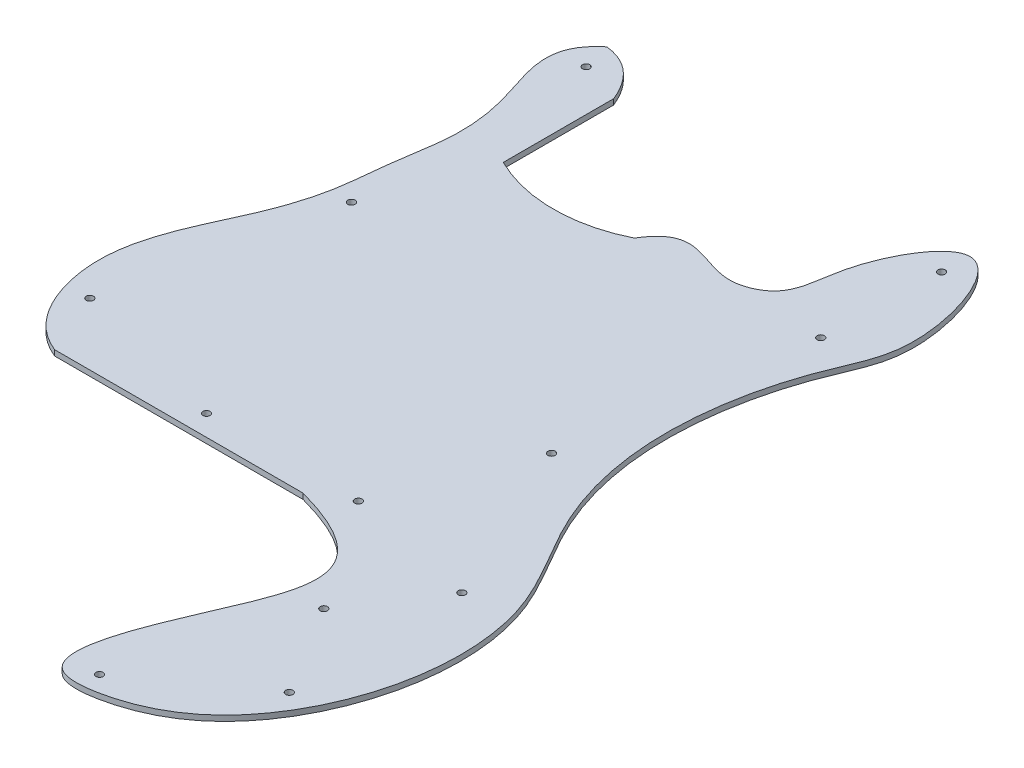
SolidWorks part; units mm, degrees
ref_plane "Front Plane" through (0, 0, 0) normal (0, 0, 1) x (1, 0, 0)
ref_plane "Top Plane" through (0, 0, 0) normal (0, 1, 0) x (1, 0, 0)
ref_plane "Right Plane" through (0, 0, 0) normal (1, 0, 0) x (0, 0, -1)
sketch "Sketch1" plane through (0, 0, 0) normal (0, 1, 0) x (1, 0, 0)
  line L0 (0, 0) -> (114.3, 0)
  line L1 (88.9, 0) -> (88.9, 254) construction
  line L2 (28.575, 228.6) -> (28.575, 177.8)
  line L3 (58.7375, 238.2047) -> (58.7375, 170.688) construction
  line L4 (88.9, 177.8) -> (88.9, 186.182)
  arc A0 (28.575, 177.8) -> (88.9, 177.8) centre (58.7375, 238.2047) ccw
  circle A1 centre (60.325, 9.525) radius 1.6764
  circle A2 centre (130.175, 9.525) radius 1.6764
  circle A3 centre (-12.3825, 28.575) radius 1.6764
  circle A4 centre (9.525, 127) radius 1.6764
  circle A5 centre (9.525, 234.95) radius 1.6764
  circle A6 centre (173.0375, 234.95) radius 1.6764
  circle A7 centre (171.45, 180.975) radius 1.6764
  circle A8 centre (155.575, 73.025) radius 1.6764
  circle A9 centre (190.5, -3.175) radius 1.6764
  circle A10 centre (190.5, -82.55) radius 1.6764
  circle A11 centre (139.7, -119.0625) radius 1.6764
  circle A12 centre (165.1, -41.275) radius 1.6764
  spline S0 degree 3 poles (0, 0) (-11.53, 4.5145) (-23.5981, 21.7649) (-27.1419, 51.1961) (-19.6131, 77.0698) (-7.4978, 100.9452) (1.0987, 126.4824) (2.5386, 152.4514) (7.7782, 177.7738) (3.4996, 210.5141) (-10.048, 234.3249) (6.35, 247.65) knots 0 0 0 0 0.130339 0.226964 0.325793 0.430447 0.530898 0.627523 0.724148 0.820773 1 1 1 1
  spline S1 degree 2 poles (6.35, 247.65) (21.4241, 246.03) (28.575, 228.6) knots 0 0 0 1 1 1
  spline S2 degree 3 poles (114.3, 0) (170.6232, -15.3245) (142.7785, -51.0148) (117.0724, -130.8654) (166.9104, -124.7473) (211.27, -85.6481) (223.2542, -5.8432) (185.8262, 45.0847) (168.8927, 100.7019) (177.4566, 154.683) (201.0165, 201.5584) (177.94, 271.8374) (147.1181, 218.1363) (148.1281, 189.8298) (118.7164, 176.4979) (100.9796, 198.2106) (88.9, 177.8) knots 0 0 0 0 0.148093 0.210363 0.240169 0.32198 0.461111 0.528033 0.586689 0.706182 0.742682 0.823051 0.881913 0.917689 0.939313 1 1 1 1
  point P6 (88.9, 12.7)
  point P8 (88.9, 25.4)
  point P10 (88.9, 50.8)
  point P12 (88.9, 76.2)
  point P13 (88.9, 177.8)
  point P15 (88.9, 177.8)
  point P16 (88.9, 101.6)
  point P17 (88.9, 127)
  point P18 (88.9, 152.4)
  point P19 (88.9, 247.65)
  point P20 (88.9, 203.2)
  point P40 (88.9, 228.6)
  point P59 (108.0008, 187.7256)
  point P61 (134.6404, 177.8)
  point P63 (173.0375, 247.65)
  point P65 (149.818, 213.3726)
  point P67 (142.5036, 189.2958)
  point P69 (128.6365, 183.048)
  dimension "D27" = 3.3528
  dimension "D39" = 50.8
  dimension "D40" = 119.0625
  dimension "D41" = 101.6
  dimension "D42" = 82.55
  dimension "D47" = 180.975
  dimension "D48" = 82.55
  dimension "D49" = 84.1375
  dimension "D1" = 114.3
  dimension "D2" = 25.4
  dimension "D3" = 12.7
  dimension "D4" = 25.4
  dimension "D5" = 50.8
  dimension "D6" = 76.2
  dimension "D8" = 25.4
  dimension "D9" = 25.4
  dimension "D10" = 254
  dimension "D11" = 25.4
  dimension "D12" = 104.775
  dimension "D13" = 111.125
  dimension "D14" = 114.3
  dimension "D15" = 107.95
  dimension "D16" = 96.8375
  dimension "D17" = 88.9
  dimension "D18" = 85.725
  dimension "D19" = 82.55
  dimension "D20" = 85.725
  dimension "D21" = 92.075
  dimension "D22" = 247.65
  dimension "D23" = 82.55
  dimension "D24" = 60.325
  dimension "D25" = 7.112
  dimension "D26" = 8.382
  dimension "D28" = 79.375
  dimension "D29" = 234.95
  dimension "D30" = 79.375
  dimension "D31" = 127
  dimension "D32" = 28.575
  dimension "D33" = 101.2825
  dimension "D34" = 28.575
  dimension "D35" = 9.525
  dimension "D36" = 69.85
  dimension "D37" = 41.275
  dimension "D38" = 76.2
  dimension "D43" = 101.6
  dimension "D44" = 3.175
  dimension "D45" = 66.675
  dimension "D46" = 73.025
  dimension "D7" = 6
extrude "Boss-Extrude1" add sketch "Sketch1" along normal blind 2.54 contours L0 S2 A0 L2 S1 S0 A1 A2 A3 A4 A5 A7 A8 A9 A10 A11 A12 region at (103.8769, 0, -72.0572)
